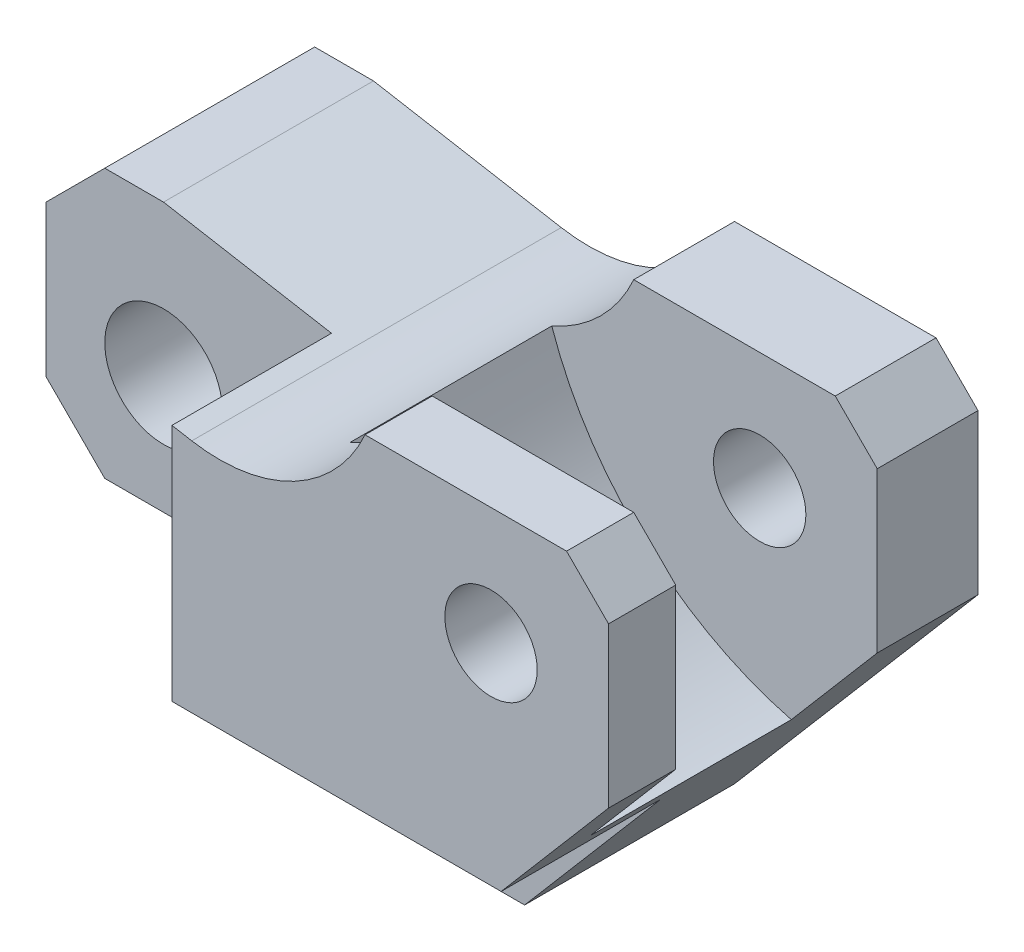
SolidWorks part; units mm, degrees
material "AISI 1020"
ref_plane "Plan de face" through (0, 0, 0) normal (0, 0, 1) x (1, 0, 0)
ref_plane "Plan de dessus" through (0, 0, 0) normal (0, 1, 0) x (1, 0, 0)
ref_plane "Plan de droite" through (0, 0, 0) normal (1, 0, 0) x (0, 0, -1)
sketch "Esquisse1" plane through (0, 0, 0) normal (0, 0, 1) x (1, 0, 0)
  line L0 (40.0103, -4.2308) -> (64.0103, -4.2308)
  line L1 (64.0103, -4.2308) -> (69.0103, -9.2308)
  line L2 (69.0103, -9.2308) -> (69.0103, -28.2308)
  line L3 (69.0103, -28.2308) -> (40.0103, -62.2308)
  line L4 (40.0103, -62.2308) -> (34.3073, -62.2308)
  line L6 (22.5858, -43.2308) -> (-9.9897, -43.2308)
  line L7 (-9.9897, -43.2308) -> (-16.9897, -36.2308)
  line L8 (-16.9897, -36.2308) -> (-16.9897, -18.2308)
  line L9 (-16.9897, -18.2308) -> (-9.9897, -11.2308)
  line L12 (-9.9897, -11.2308) -> (-2.9897, -11.2308)
  line L18 (-2.9897, -11.2308) -> (19.3717, -15.1737)
  arc A1 (27.5315, -47.4955) -> (22.5858, -43.2308) centre (22.5858, -48.2308) ccw
  arc A2 (40.0103, -4.2308) -> (19.3717, -15.1737) centre (22.671, 3.5376) cw
  arc A3 (34.3073, -62.2308) -> (27.5315, -47.4955) centre (56.2162, -43.2308) cw
  circle A4 centre (-2.9897, -29.2308) radius 7
  point P17 (24.1901, -43.2308)
  dimension "D15" = 5
  dimension "D17" = 29
  dimension "D1" = 29
  dimension "D2" = 24
  dimension "D3" = 58
  dimension "D4" = 5
  dimension "D5" = 7
  dimension "D6" = 32
  dimension "D7" = 7
  dimension "D8" = 19
  dimension "D10" = 135
  dimension "D11" = 86
  dimension "D13" = 135
  dimension "D12" = 14
  dimension "D14" = 29
  dimension "D16" = 190
  dimension "D18" = 14
  dimension "D19" = 14
  dimension "D20" = 135
  dimension "D9" = 19
  dimension "D21" = 19
extrude "Boss.-Extru.2" add sketch "Esquisse1" along normal blind 44
sketch "Esquisse2" plane through (0, 0, 44) normal (0, 0, 1) x (1, 0, 0)
  line L0 (17.0103, -43.2308) -> (17.0103, -14.7574)
  line L1 (-9.9897, -43.2308) -> (22.5858, -43.2308) construction
  line L2 (19.3717, -15.1737) -> (-2.9897, -11.2308) construction
  line L3 (56.2162, -43.2308) -> (40.0103, -62.2308)
  line L4 (69.0103, -28.2308) -> (69.0103, -9.2308) construction
  line L5 (22.5858, -43.2308) -> (56.2162, -43.2308)
  line L6 (40.0103, -62.2308) -> (69.0103, -28.2308) construction
  line L7 (40.0103, -62.2308) -> (34.3073, -62.2308)
  line L8 (17.0103, -14.7574) -> (-2.9897, -11.2308)
  line L9 (-2.9897, -11.2308) -> (-9.9897, -11.2308)
  line L10 (-9.9897, -11.2308) -> (-16.9897, -18.2308)
  line L11 (-16.9897, -18.2308) -> (-16.9897, -36.2308)
  line L12 (-16.9897, -36.2308) -> (-9.9897, -43.2308)
  line L13 (-9.9897, -43.2308) -> (17.0103, -43.2308)
  line L15 (22.5858, -43.2308) -> (23.0527, -46.7092)
  line L16 (23.0527, -46.7092) -> (29.1462, -61.7851)
  line L17 (29.1462, -61.7851) -> (34.3073, -62.2308)
  arc A0 (34.3073, -62.2308) -> (27.4847, -47.1684) centre (56.2162, -43.2308) cw
  line M10 (19.3717, -15.1737) -> (-2.9897, -11.2308)
  line M11 (-2.9897, -11.2308) -> (-9.9897, -11.2308)
  line M12 (-9.9897, -11.2308) -> (-16.9897, -18.2308)
  line M13 (-16.9897, -18.2308) -> (-16.9897, -36.2308)
  line M14 (-16.9897, -36.2308) -> (-9.9897, -43.2308)
  line M15 (-9.9897, -43.2308) -> (22.5858, -43.2308)
  arc M16 (22.5858, -43.2308) -> (27.5315, -47.4955) centre (22.5858, -48.2308) cw
  arc M17 (27.5315, -47.4955) -> (34.3073, -62.2308) centre (56.2162, -43.2308) ccw
  line M18 (34.3073, -62.2308) -> (40.0103, -62.2308)
  line M19 (40.0103, -62.2308) -> (69.0103, -28.2308)
  circle M23 centre (-2.9897, -29.2308) radius 7
  dimension "D1" = 52
extrude "Enlèv. mat.-Extru.1" cut sketch "Esquisse2" against normal blind 19 contours L0 M15 M10 M11 M12 M13 M14 M23 region at (3.5103, -42.7639, 44)
extrude "Enlèv. mat.-Extru.2" cut sketch "Esquisse2<4>" against normal blind 19 contours L5 M16 M17 M18 M19 region at (39.1003, -50.6947, 44)
sketch "Esquisse2<4>" plane through (0, 0, 44) normal (0, 0, 1) x (1, 0, 0) same geometry as "Esquisse2"
sketch "Esquisse3" plane through (0, 0, 44) normal (0, 0, 1) x (1, 0, 0)
  line L0 (64.0103, -4.2308) -> (40.0103, -4.2308) construction
  line L2 (69.0103, -28.2308) -> (69.0103, -9.2308) construction
  circle A0 centre (55.0103, -18.2308) radius 5.5
  point P6 (45.2144, -20.2124)
  dimension "D1" = 14
  dimension "D2" = 14
extrude "Enlèv. mat.-Extru.3" cut sketch "Esquisse3" against normal through all contours A0
sketch "Esquisse4" plane through (0, -4.2308, 0) normal (0, 1, 0) x (1, 0, 0)
  line L0 (40.0103, -12) -> (63.6421, -12)
  line L1 (40.0103, -44) -> (40.0103, 0) construction
  line L2 (40.0103, -36) -> (64.3668, -36)
  line L3 (64.0103, 0) -> (40.0103, 0) construction
  dimension "D1" = 24
  dimension "D2" = 12
sketch "Esquisse5" plane through (69.0103, 0, 0) normal (1, 0, 0) x (0, 0, -1)
  line L1 (-36, -40.3011) -> (-12, -40.3011)
  line L2 (-12, -40.3011) -> (-12, -4.2308)
  line L3 (-44, -4.2308) -> (0, -4.2308) construction
  line L5 (0, -9.2308) -> (0, -4.2308) construction
  line L6 (-36, -4.3011) -> (-36, 0.6989)
  line L7 (-36, 0.6989) -> (-12, 0.6989)
  line L8 (-12, 0.6989) -> (-12, -4.2308)
  dimension "D1" = 36
  dimension "D2" = 24
  dimension "D3" = 12
  dimension "D4" = 41
ref_plane "Plan18" through (0, 0, 12) normal (0, 0, -1) x (-1, 0, 0)
sketch "Esquisse8" plane through (0, 0, 12) normal (0, 0, -1) x (-1, 0, 0)
  line L0 (-69.0103, -40.3011) -> (-69.0103, -4.2308) construction
  line L15 (-40.0103, -4.2308) -> (-64.0103, -4.2308)
  line L16 (-64.0103, -4.2308) -> (-69.0103, -9.2308)
  line L17 (-69.0103, -9.2308) -> (-69.0103, -28.2308)
  line L18 (-69.0103, -28.2308) -> (-40.0103, -62.2308)
  line L19 (-40.0103, -62.2308) -> (-34.3073, -62.2308)
  line L20 (-22.5858, -43.2308) -> (9.9897, -43.2308)
  line L21 (9.9897, -43.2308) -> (16.9897, -36.2308)
  line L22 (16.9897, -36.2308) -> (16.9897, -18.2308)
  line L23 (16.9897, -18.2308) -> (9.9897, -11.2308)
  line L24 (9.9897, -11.2308) -> (2.9897, -11.2308)
  line L25 (2.9897, -11.2308) -> (-19.3717, -15.1737)
  line L26 (-40.0103, -4.2308) -> (-64.0103, -4.2308)
  line L27 (-64.0103, -4.2308) -> (-69.0103, -9.2308)
  line L28 (-69.0103, -9.2308) -> (-69.0103, -28.2308)
  line L29 (-69.0103, -28.2308) -> (-40.0103, -62.2308)
  line L30 (-40.0103, -62.2308) -> (-34.3073, -62.2308)
  line L31 (-22.5858, -43.2308) -> (9.9897, -43.2308)
  line L32 (9.9897, -43.2308) -> (16.9897, -36.2308)
  line L33 (16.9897, -36.2308) -> (16.9897, -18.2308)
  line L34 (16.9897, -18.2308) -> (9.9897, -11.2308)
  line L35 (9.9897, -11.2308) -> (2.9897, -11.2308)
  line L36 (2.9897, -11.2308) -> (-19.3717, -15.1737)
  circle A0 centre (-69.0103, -0.5289) radius 41
  arc A4 (-40.0103, -4.2308) -> (-19.3717, -15.1737) centre (-22.671, 3.5376) ccw
  arc A5 (-34.3073, -62.2308) -> (-27.5315, -47.4955) centre (-56.2162, -43.2308) ccw
  arc A6 (-22.5858, -43.2308) -> (-27.5315, -47.4955) centre (-22.5858, -48.2308) ccw
  arc A7 (-40.0103, -4.2308) -> (-19.3717, -15.1737) centre (-22.671, 3.5376) ccw
  arc A8 (-34.3073, -62.2308) -> (-27.5315, -47.4955) centre (-56.2162, -43.2308) ccw
  arc A9 (-22.5858, -43.2308) -> (-27.5315, -47.4955) centre (-22.5858, -48.2308) ccw
  point P4 (0, 0)
  point P6 (-58.775, -40.2308)
  dimension "D1" = 0
  dimension "D2" = 36
extrude "Enlèv. mat.-Extru.21" cut sketch "Esquisse8" against normal blind 24 contours A7 L26 L27 L28 L29 A0 region at (52.1987, -19.7995, 12)
equation "\"A\" = 86"
equation "\"B\" = 58"
equation "\"C\" = 44"
equation "\"D11@Esquisse1\"=\"A\""
equation "\"D3@Esquisse1\"=\"B\""
equation "\"D1@Boss.-Extru.2\"=\"C\""
